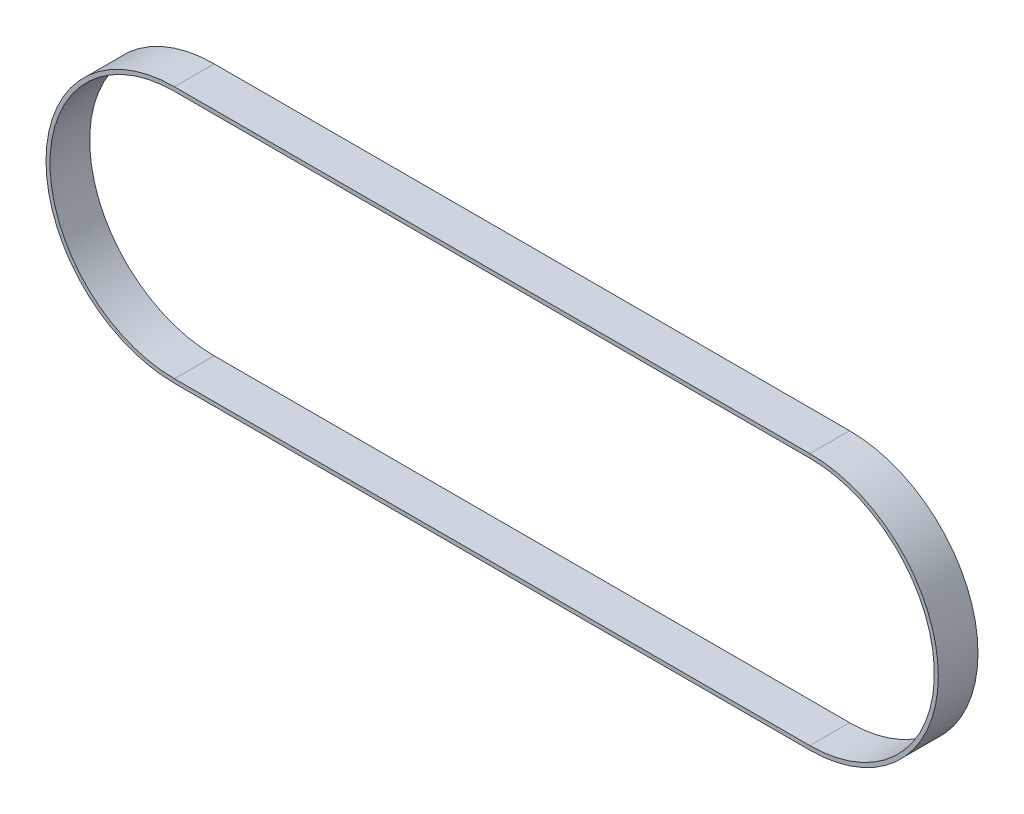
SolidWorks part; units mm, degrees
ref_plane "1" through (0, 0, 0) normal (0, 0, 1) x (1, 0, 0)
ref_plane "2" through (0, 0, 0) normal (0, 1, 0) x (1, 0, 0)
ref_plane "3" through (0, 0, 0) normal (1, 0, 0) x (0, 0, -1)
ref_plane "Front Plane" through (0, 0, 0) normal (0, -1, 0) x (1, 0, 0)
ref_plane "Right Plane" through (0, 0, 0) normal (1, 0, 0) x (0, 1, 0)
ref_plane "Top Plane" through (0, 0, 0) normal (0, 0, 1) x (1, 0, 0)
ref_axis "Axis1" through (0, 0, 50.7014) along (0, 0, -1)
sketch "Sketch1" plane through (0, 0, 0) normal (0, 0, 1) x (1, 0, 0)
  line L0 (0, 0) -> (96, 0) construction
  line L1 (0, 19.1) -> (96, 19.1) construction
  line L2 (0, -19.1) -> (96, -19.1) construction
  line L3 (0, 18.8) -> (96, 18.8)
  line L4 (0, -18.8) -> (96, -18.8)
  line L5 (0, -19.4) -> (96, -19.4)
  line L6 (0, 19.4) -> (96, 19.4)
  arc A0 (0, 19.1) -> (0, -19.1) centre (0, 0) ccw construction
  arc A1 (96, -19.1) -> (96, 19.1) centre (96, 0) ccw construction
  arc A2 (96, -18.8) -> (96, 18.8) centre (96, 0) ccw
  arc A3 (0, 18.8) -> (0, -18.8) centre (0, 0) ccw
  arc A4 (0, 19.4) -> (0, -19.4) centre (0, 0) ccw
  arc A5 (96, -19.4) -> (96, 19.4) centre (96, 0) ccw
  point P2 (48, 0)
  dimension "D2" = 38.2
  dimension "D1" = 96
  dimension "D3" = 0.3
  dimension "D4" = 0.6
extrude "Boss-Extrude1" add sketch "Sketch1" along normal mid plane 6
